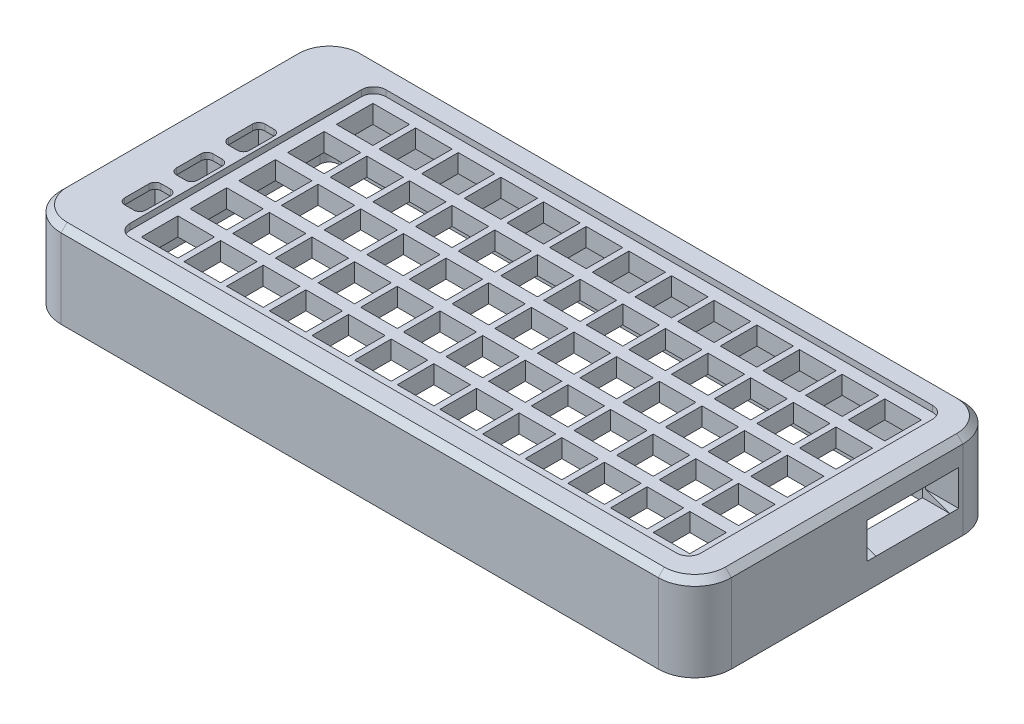
SolidWorks part; units mm, degrees
ref_plane "前视基准面" through (0, 0, 0) normal (0, 0, 1) x (1, 0, 0)
ref_plane "上视基准面" through (0, 0, 0) normal (0, 1, 0) x (1, 0, 0)
ref_plane "右视基准面" through (0, 0, 0) normal (1, 0, 0) x (0, 0, -1)
other "Configuration Table"
sketch "草图1" plane through (0, 0, 0) normal (0, 1, 0) x (1, 0, 0)
  line L1 (-55, -25) -> (55, -25)
  line L2 (-55, -25) -> (-55, 25)
  line L3 (-55, 25) -> (55, 25)
  line L4 (55, -25) -> (55, 25)
  line L5 (-55, -25) -> (55, 25) construction
  line L6 (-55, 25) -> (55, -25) construction
  point P0 (0, 0)
  dimension "D1" = 50
  dimension "D2" = 110
extrude "凸台-拉伸1" add sketch "草图1" along normal blind 3
sketch "草图2" plane through (0, 0, 0) normal (0, -1, 0) x (1, 0, 0)
  line L0 (46.3251, 14.2) -> (44.0251, 17.8) construction
  line L1 (48.1751, 11) -> (48.1751, 5)
  line L2 (48.1751, 19) -> (42.1751, 19)
  line L3 (48.1751, 19) -> (48.1751, 13)
  line L4 (48.1751, 13) -> (42.1751, 13)
  line L5 (42.1751, 19) -> (42.1751, 13)
  line L6 (48.1751, 19) -> (42.1751, 13) construction
  line L7 (48.1751, 13) -> (42.1751, 19) construction
  line L8 (48.1751, 5) -> (42.1751, 5)
  line L9 (42.1751, 11) -> (42.1751, 5)
  line L10 (48.1751, 11) -> (42.1751, 11)
  line L11 (48.1751, 3) -> (48.1751, -3)
  line L12 (48.1751, -3) -> (42.1751, -3)
  line L13 (42.1751, 3) -> (42.1751, -3)
  line L14 (48.1751, 3) -> (42.1751, 3)
  line L15 (48.1751, -5) -> (48.1751, -11)
  line L16 (48.1751, -11) -> (42.1751, -11)
  line L17 (42.1751, -5) -> (42.1751, -11)
  line L18 (48.1751, -5) -> (42.1751, -5)
  line L19 (48.1751, -13) -> (48.1751, -19)
  line L20 (48.1751, -19) -> (42.1751, -19)
  line L21 (42.1751, -13) -> (42.1751, -19)
  line L22 (48.1751, -13) -> (42.1751, -13)
  line L23 (41.1751, 11) -> (41.1751, 5)
  line L24 (41.1751, 5) -> (35.1751, 5)
  line L25 (35.1751, 11) -> (35.1751, 5)
  line L26 (41.1751, 11) -> (35.1751, 11)
  line L27 (41.1751, 3) -> (41.1751, -3)
  line L28 (41.1751, -3) -> (35.1751, -3)
  line L29 (35.1751, 3) -> (35.1751, -3)
  line L30 (41.1751, 3) -> (35.1751, 3)
  line L31 (41.1751, -5) -> (41.1751, -11)
  line L32 (41.1751, -11) -> (35.1751, -11)
  line L33 (35.1751, -5) -> (35.1751, -11)
  line L34 (41.1751, -5) -> (35.1751, -5)
  line L35 (41.1751, -13) -> (41.1751, -19)
  line L36 (41.1751, -19) -> (35.1751, -19)
  line L37 (35.1751, -13) -> (35.1751, -19)
  line L38 (41.1751, -13) -> (35.1751, -13)
  line L39 (34.1751, 11) -> (34.1751, 5)
  line L40 (34.1751, 5) -> (28.1751, 5)
  line L41 (28.1751, 11) -> (28.1751, 5)
  line L42 (34.1751, 11) -> (28.1751, 11)
  line L43 (34.1751, 3) -> (34.1751, -3)
  line L44 (34.1751, -3) -> (28.1751, -3)
  line L45 (28.1751, 3) -> (28.1751, -3)
  line L46 (34.1751, 3) -> (28.1751, 3)
  line L47 (34.1751, -5) -> (34.1751, -11)
  line L48 (34.1751, -11) -> (28.1751, -11)
  line L49 (28.1751, -5) -> (28.1751, -11)
  line L50 (34.1751, -5) -> (28.1751, -5)
  line L51 (34.1751, -13) -> (34.1751, -19)
  line L52 (34.1751, -19) -> (28.1751, -19)
  line L53 (28.1751, -13) -> (28.1751, -19)
  line L54 (34.1751, -13) -> (28.1751, -13)
  line L55 (27.1751, 11) -> (27.1751, 5)
  line L56 (27.1751, 5) -> (21.1751, 5)
  line L57 (21.1751, 11) -> (21.1751, 5)
  line L58 (27.1751, 11) -> (21.1751, 11)
  line L59 (27.1751, 3) -> (27.1751, -3)
  line L60 (27.1751, -3) -> (21.1751, -3)
  line L61 (21.1751, 3) -> (21.1751, -3)
  line L62 (27.1751, 3) -> (21.1751, 3)
  line L63 (27.1751, -5) -> (27.1751, -11)
  line L64 (27.1751, -11) -> (21.1751, -11)
  line L65 (21.1751, -5) -> (21.1751, -11)
  line L66 (27.1751, -5) -> (21.1751, -5)
  line L67 (27.1751, -13) -> (27.1751, -19)
  line L68 (27.1751, -19) -> (21.1751, -19)
  line L69 (21.1751, -13) -> (21.1751, -19)
  line L70 (27.1751, -13) -> (21.1751, -13)
  line L71 (20.1751, 11) -> (20.1751, 5)
  line L72 (20.1751, 5) -> (14.1751, 5)
  line L73 (14.1751, 11) -> (14.1751, 5)
  line L74 (20.1751, 11) -> (14.1751, 11)
  line L75 (20.1751, 3) -> (20.1751, -3)
  line L76 (20.1751, -3) -> (14.1751, -3)
  line L77 (14.1751, 3) -> (14.1751, -3)
  line L78 (20.1751, 3) -> (14.1751, 3)
  line L79 (20.1751, -5) -> (20.1751, -11)
  line L80 (20.1751, -11) -> (14.1751, -11)
  line L81 (14.1751, -5) -> (14.1751, -11)
  line L82 (20.1751, -5) -> (14.1751, -5)
  line L83 (20.1751, -13) -> (20.1751, -19)
  line L84 (20.1751, -19) -> (14.1751, -19)
  line L85 (14.1751, -13) -> (14.1751, -19)
  line L86 (20.1751, -13) -> (14.1751, -13)
  line L87 (13.1751, 11) -> (13.1751, 5)
  line L88 (13.1751, 5) -> (7.1751, 5)
  line L89 (7.1751, 11) -> (7.1751, 5)
  line L90 (13.1751, 11) -> (7.1751, 11)
  line L91 (13.1751, 3) -> (13.1751, -3)
  line L92 (13.1751, -3) -> (7.1751, -3)
  line L93 (7.1751, 3) -> (7.1751, -3)
  line L94 (13.1751, 3) -> (7.1751, 3)
  line L95 (13.1751, -5) -> (13.1751, -11)
  line L96 (13.1751, -11) -> (7.1751, -11)
  line L97 (7.1751, -5) -> (7.1751, -11)
  line L98 (13.1751, -5) -> (7.1751, -5)
  line L99 (13.1751, -13) -> (13.1751, -19)
  line L100 (13.1751, -19) -> (7.1751, -19)
  line L101 (7.1751, -13) -> (7.1751, -19)
  line L102 (13.1751, -13) -> (7.1751, -13)
  line L103 (6.1751, 11) -> (6.1751, 5)
  line L104 (6.1751, 5) -> (0.1751, 5)
  line L105 (0.1751, 11) -> (0.1751, 5)
  line L106 (6.1751, 11) -> (0.1751, 11)
  line L107 (6.1751, 3) -> (6.1751, -3)
  line L108 (6.1751, -3) -> (0.1751, -3)
  line L109 (0.1751, 3) -> (0.1751, -3)
  line L110 (6.1751, 3) -> (0.1751, 3)
  line L111 (6.1751, -5) -> (6.1751, -11)
  line L112 (6.1751, -11) -> (0.1751, -11)
  line L113 (0.1751, -5) -> (0.1751, -11)
  line L114 (6.1751, -5) -> (0.1751, -5)
  line L115 (6.1751, -13) -> (6.1751, -19)
  line L116 (6.1751, -19) -> (0.1751, -19)
  line L117 (0.1751, -13) -> (0.1751, -19)
  line L118 (6.1751, -13) -> (0.1751, -13)
  line L119 (-0.8249, 11) -> (-0.8249, 5)
  line L120 (-0.8249, 5) -> (-6.8249, 5)
  line L121 (-6.8249, 11) -> (-6.8249, 5)
  line L122 (-0.8249, 11) -> (-6.8249, 11)
  line L123 (-0.8249, 3) -> (-0.8249, -3)
  line L124 (-0.8249, -3) -> (-6.8249, -3)
  line L125 (-6.8249, 3) -> (-6.8249, -3)
  line L126 (-0.8249, 3) -> (-6.8249, 3)
  line L127 (-0.8249, -5) -> (-0.8249, -11)
  line L128 (-0.8249, -11) -> (-6.8249, -11)
  line L129 (-6.8249, -5) -> (-6.8249, -11)
  line L130 (-0.8249, -5) -> (-6.8249, -5)
  line L131 (-0.8249, -13) -> (-0.8249, -19)
  line L132 (-0.8249, -19) -> (-6.8249, -19)
  line L133 (-6.8249, -13) -> (-6.8249, -19)
  line L134 (-0.8249, -13) -> (-6.8249, -13)
  line L135 (-7.8249, 11) -> (-7.8249, 5)
  line L136 (-7.8249, 5) -> (-13.8249, 5)
  line L137 (-13.8249, 11) -> (-13.8249, 5)
  line L138 (-7.8249, 11) -> (-13.8249, 11)
  line L139 (-7.8249, 3) -> (-7.8249, -3)
  line L140 (-7.8249, -3) -> (-13.8249, -3)
  line L141 (-13.8249, 3) -> (-13.8249, -3)
  line L142 (-7.8249, 3) -> (-13.8249, 3)
  line L143 (-7.8249, -5) -> (-7.8249, -11)
  line L144 (-7.8249, -11) -> (-13.8249, -11)
  line L145 (-13.8249, -5) -> (-13.8249, -11)
  line L146 (-7.8249, -5) -> (-13.8249, -5)
  line L147 (-7.8249, -13) -> (-7.8249, -19)
  line L148 (-7.8249, -19) -> (-13.8249, -19)
  line L149 (-13.8249, -13) -> (-13.8249, -19)
  line L150 (-7.8249, -13) -> (-13.8249, -13)
  line L151 (-14.8249, 11) -> (-14.8249, 5)
  line L152 (-14.8249, 5) -> (-20.8249, 5)
  line L153 (-20.8249, 11) -> (-20.8249, 5)
  line L154 (-14.8249, 11) -> (-20.8249, 11)
  line L155 (-14.8249, 3) -> (-14.8249, -3)
  line L156 (-14.8249, -3) -> (-20.8249, -3)
  line L157 (-20.8249, 3) -> (-20.8249, -3)
  line L158 (-14.8249, 3) -> (-20.8249, 3)
  line L159 (-14.8249, -5) -> (-14.8249, -11)
  line L160 (-14.8249, -11) -> (-20.8249, -11)
  line L161 (-20.8249, -5) -> (-20.8249, -11)
  line L162 (-14.8249, -5) -> (-20.8249, -5)
  line L163 (-14.8249, -13) -> (-14.8249, -19)
  line L164 (-14.8249, -19) -> (-20.8249, -19)
  line L165 (-20.8249, -13) -> (-20.8249, -19)
  line L166 (-14.8249, -13) -> (-20.8249, -13)
  line L167 (-21.8249, 11) -> (-21.8249, 5)
  line L168 (-21.8249, 5) -> (-27.8249, 5)
  line L169 (-27.8249, 11) -> (-27.8249, 5)
  line L170 (-21.8249, 11) -> (-27.8249, 11)
  line L171 (-21.8249, 3) -> (-21.8249, -3)
  line L172 (-21.8249, -3) -> (-27.8249, -3)
  line L173 (-27.8249, 3) -> (-27.8249, -3)
  line L174 (-21.8249, 3) -> (-27.8249, 3)
  line L175 (-21.8249, -5) -> (-21.8249, -11)
  line L176 (-21.8249, -11) -> (-27.8249, -11)
  line L177 (-27.8249, -5) -> (-27.8249, -11)
  line L178 (-21.8249, -5) -> (-27.8249, -5)
  line L179 (-21.8249, -13) -> (-21.8249, -19)
  line L180 (-21.8249, -19) -> (-27.8249, -19)
  line L181 (-27.8249, -13) -> (-27.8249, -19)
  line L182 (-21.8249, -13) -> (-27.8249, -13)
  line L183 (-28.8249, 11) -> (-28.8249, 5)
  line L184 (-28.8249, 5) -> (-34.8249, 5)
  line L185 (-34.8249, 11) -> (-34.8249, 5)
  line L186 (-28.8249, 11) -> (-34.8249, 11)
  line L187 (-28.8249, 3) -> (-28.8249, -3)
  line L188 (-28.8249, -3) -> (-34.8249, -3)
  line L189 (-34.8249, 3) -> (-34.8249, -3)
  line L190 (-28.8249, 3) -> (-34.8249, 3)
  line L191 (-28.8249, -5) -> (-28.8249, -11)
  line L192 (-28.8249, -11) -> (-34.8249, -11)
  line L193 (-34.8249, -5) -> (-34.8249, -11)
  line L194 (-28.8249, -5) -> (-34.8249, -5)
  line L195 (-28.8249, -13) -> (-28.8249, -19)
  line L196 (-28.8249, -19) -> (-34.8249, -19)
  line L197 (-34.8249, -13) -> (-34.8249, -19)
  line L198 (-28.8249, -13) -> (-34.8249, -13)
  line L199 (-35.8249, 11) -> (-35.8249, 5)
  line L200 (-35.8249, 5) -> (-41.8249, 5)
  line L201 (-41.8249, 11) -> (-41.8249, 5)
  line L202 (-35.8249, 11) -> (-41.8249, 11)
  line L203 (-35.8249, 3) -> (-35.8249, -3)
  line L204 (-35.8249, -3) -> (-41.8249, -3)
  line L205 (-41.8249, 3) -> (-41.8249, -3)
  line L206 (-35.8249, 3) -> (-41.8249, 3)
  line L207 (-35.8249, -5) -> (-35.8249, -11)
  line L208 (-35.8249, -11) -> (-41.8249, -11)
  line L209 (-41.8249, -5) -> (-41.8249, -11)
  line L210 (-35.8249, -5) -> (-41.8249, -5)
  line L211 (-35.8249, -13) -> (-35.8249, -19)
  line L212 (-35.8249, -19) -> (-41.8249, -19)
  line L213 (-41.8249, -13) -> (-41.8249, -19)
  line L214 (-35.8249, -13) -> (-41.8249, -13)
  line L215 (41.1751, 19) -> (41.1751, 13)
  line L216 (41.1751, 13) -> (35.1751, 13)
  line L217 (35.1751, 19) -> (35.1751, 13)
  line L218 (41.1751, 19) -> (35.1751, 19)
  line L219 (34.1751, 19) -> (34.1751, 13)
  line L220 (34.1751, 13) -> (28.1751, 13)
  line L221 (28.1751, 19) -> (28.1751, 13)
  line L222 (34.1751, 19) -> (28.1751, 19)
  line L223 (27.1751, 19) -> (27.1751, 13)
  line L224 (27.1751, 13) -> (21.1751, 13)
  line L225 (21.1751, 19) -> (21.1751, 13)
  line L226 (27.1751, 19) -> (21.1751, 19)
  line L227 (20.1751, 19) -> (20.1751, 13)
  line L228 (20.1751, 13) -> (14.1751, 13)
  line L229 (14.1751, 19) -> (14.1751, 13)
  line L230 (20.1751, 19) -> (14.1751, 19)
  line L231 (13.1751, 19) -> (13.1751, 13)
  line L232 (13.1751, 13) -> (7.1751, 13)
  line L233 (7.1751, 19) -> (7.1751, 13)
  line L234 (13.1751, 19) -> (7.1751, 19)
  line L235 (6.1751, 19) -> (6.1751, 13)
  line L236 (6.1751, 13) -> (0.1751, 13)
  line L237 (0.1751, 19) -> (0.1751, 13)
  line L238 (6.1751, 19) -> (0.1751, 19)
  line L239 (-0.8249, 19) -> (-0.8249, 13)
  line L240 (-0.8249, 13) -> (-6.8249, 13)
  line L241 (-6.8249, 19) -> (-6.8249, 13)
  line L242 (-0.8249, 19) -> (-6.8249, 19)
  line L243 (-7.8249, 19) -> (-7.8249, 13)
  line L244 (-7.8249, 13) -> (-13.8249, 13)
  line L245 (-13.8249, 19) -> (-13.8249, 13)
  line L246 (-7.8249, 19) -> (-13.8249, 19)
  line L247 (-14.8249, 19) -> (-14.8249, 13)
  line L248 (-14.8249, 13) -> (-20.8249, 13)
  line L249 (-20.8249, 19) -> (-20.8249, 13)
  line L250 (-14.8249, 19) -> (-20.8249, 19)
  line L251 (-21.8249, 19) -> (-21.8249, 13)
  line L252 (-21.8249, 13) -> (-27.8249, 13)
  line L253 (-27.8249, 19) -> (-27.8249, 13)
  line L254 (-21.8249, 19) -> (-27.8249, 19)
  line L255 (-28.8249, 19) -> (-28.8249, 13)
  line L256 (-28.8249, 13) -> (-34.8249, 13)
  line L257 (-34.8249, 19) -> (-34.8249, 13)
  line L258 (-28.8249, 19) -> (-34.8249, 19)
  line L259 (-35.8249, 19) -> (-35.8249, 13)
  line L260 (-35.8249, 13) -> (-41.8249, 13)
  line L261 (-41.8249, 19) -> (-41.8249, 13)
  line L262 (-35.8249, 19) -> (-41.8249, 19)
  point P2 (45.1751, 16)
  dimension "D1" = 6
  dimension "D2" = 6
  dimension "D3" = 5
  dimension "D4" = 13
extrude "切除-拉伸1" cut sketch "草图2" against normal blind 10
sketch "草图3" plane through (0, 3, 0) normal (0, 1, 0) x (1, 0, 0)
  line L0 (-55, 25) -> (-55, -25) construction
  line L1 (-55, 25) -> (55, 25)
  line L2 (-55, 25) -> (-55, -25)
  line L3 (-55, -25) -> (55, -25)
  line L4 (55, 25) -> (55, -25)
  line L5 (55, 25) -> (-55, 25) construction
  line L6 (55, -25) -> (55, 25) construction
  line L7 (-55, -25) -> (55, -25) construction
  line L9 (-43.7, 21) -> (50, 21)
  line L10 (-43.7, 21) -> (-43.7, -21)
  line L11 (-43.7, -21) -> (50, -21)
  line L12 (50, 21) -> (50, -21)
  dimension "D1" = 4
  dimension "D2" = 4
  dimension "D3" = 5
  dimension "D4" = 42
  dimension "D5" = 11.3
extrude "凸台-拉伸2" add sketch "草图3" along normal blind 1
fillet "圆角1" radius 6 4 edges at (-55, 2, -25) (-55, 2, 25) (55, 2, 25) (55, 2, -25)
sketch "草图4" plane through (0, 0, 0) normal (0, -1, 0) x (1, 0, 0)
  line L0 (-45.3973, -4.764) -> (-46.6251, -1.636) construction
  line L1 (-45.3973, 3.736) -> (-46.6251, 6.864) construction
  line L2 (-45.2612, -0.2) -> (-46.7612, -0.2)
  line L3 (-44.2612, -1.2) -> (-44.2612, -5.2)
  line L4 (-45.2612, -6.2) -> (-46.7612, -6.2)
  line L5 (-47.7612, -1.2) -> (-47.7612, -5.2)
  line L6 (-44.2612, -0.2) -> (-47.7612, -6.2) construction
  line L7 (-44.2612, -6.2) -> (-47.7612, -0.2) construction
  line L8 (-44.2612, 7.3) -> (-44.2612, 3.3)
  line L9 (-45.2612, 8.3) -> (-46.7612, 8.3)
  line L10 (-47.7612, 7.3) -> (-47.7612, 3.3)
  line L11 (-45.2612, 2.3) -> (-46.7612, 2.3)
  line L12 (-45.3973, 12.236) -> (-46.6251, 15.364) construction
  line L13 (-44.2612, 15.8) -> (-44.2612, 11.8)
  line L14 (-45.2612, 16.8) -> (-46.7612, 16.8)
  line L15 (-47.7612, 15.8) -> (-47.7612, 11.8)
  line L16 (-45.2612, 10.8) -> (-46.7612, 10.8)
  arc A0 (-46.7612, 16.8) -> (-47.7612, 15.8) centre (-46.7612, 15.8) ccw
  arc A1 (-44.2612, 11.8) -> (-45.2612, 10.8) centre (-45.2612, 11.8) cw
  arc A2 (-44.2612, 15.8) -> (-45.2612, 16.8) centre (-45.2612, 15.8) ccw
  arc A3 (-47.7612, 11.8) -> (-46.7612, 10.8) centre (-46.7612, 11.8) ccw
  arc A4 (-46.7612, 8.3) -> (-47.7612, 7.3) centre (-46.7612, 7.3) ccw
  arc A5 (-44.2612, 3.3) -> (-45.2612, 2.3) centre (-45.2612, 3.3) cw
  arc A6 (-44.2612, 7.3) -> (-45.2612, 8.3) centre (-45.2612, 7.3) ccw
  arc A7 (-47.7612, 3.3) -> (-46.7612, 2.3) centre (-46.7612, 3.3) ccw
  arc A8 (-46.7612, -0.2) -> (-47.7612, -1.2) centre (-46.7612, -1.2) ccw
  arc A9 (-44.2612, -5.2) -> (-45.2612, -6.2) centre (-45.2612, -5.2) cw
  arc A10 (-45.2612, -0.2) -> (-44.2612, -1.2) centre (-45.2612, -1.2) cw
  arc A11 (-46.7612, -6.2) -> (-47.7612, -5.2) centre (-46.7612, -5.2) cw
  point P2 (-46.0112, -3.2)
  dimension "D4" = 1
  dimension "D1" = 3.5
  dimension "D2" = 6
  dimension "D3" = 3
extrude "切除-拉伸2" cut sketch "草图4" against normal blind 6
sketch "草图5" plane through (0, 0, 0) normal (0, -1, 0) x (1, 0, 0)
  line L0 (-46.0112, -6.2) -> (-46.0112, -0.2) construction
  line L1 (-46.7612, -6.2) -> (-45.2612, -6.2) construction
  line L2 (-45.2612, -0.2) -> (-46.7612, -0.2) construction
  line L3 (-43.7612, 8.8) -> (-43.7612, 1.8)
  line L4 (-43.7612, 0.3) -> (-48.2612, 0.3)
  line L5 (-43.7612, 0.3) -> (-43.7612, -6.7)
  line L6 (-43.7612, -6.7) -> (-48.2612, -6.7)
  line L7 (-48.2612, 0.3) -> (-48.2612, -6.7)
  line L8 (-43.7612, 0.3) -> (-48.2612, -6.7) construction
  line L9 (-43.7612, -6.7) -> (-48.2612, 0.3) construction
  line L10 (-43.7612, 8.8) -> (-48.2612, 8.8)
  line L11 (-48.2612, 8.8) -> (-48.2612, 1.8)
  line L12 (-43.7612, 1.8) -> (-48.2612, 1.8)
  line L13 (-43.7612, 17.3) -> (-43.7612, 10.3)
  line L14 (-43.7612, 17.3) -> (-48.2612, 17.3)
  line L15 (-48.2612, 17.3) -> (-48.2612, 10.3)
  line L16 (-43.7612, 10.3) -> (-48.2612, 10.3)
  point P6 (-46.0112, -3.2)
  dimension "D1" = 7
  dimension "D2" = 4.5
  dimension "D3" = 3
extrude "切除-拉伸3" cut sketch "草图5" against normal blind 3
fillet "圆角2" radius 2 4 edges at (50, 3.5, 21) (50, 3.5, -21) (-43.7, 3.5, -21) (-43.7, 3.5, 21)
chamfer "倒角1" distance 1 angle 45 8 edges at (53.2426, 4, -23.2426) (0, 4, -25) (55, 4, 0) (-53.2426, 4, -23.2426) (53.2426, 4, 23.2426) (-55, 4, 0) (0, 4, 25) (-53.2426, 4, 23.2426)
sketch "草图6" plane through (0, 0, 0) normal (0, -1, 0) x (1, 0, 0)
  line L6 (-55, 19) -> (-55, -19)
  line L7 (-49, -25) -> (49, -25)
  line L8 (-55, 19) -> (-55, -19)
  line L9 (-49, -25) -> (49, -25)
  line L10 (55, 19) -> (55, -19)
  line L11 (55, 19) -> (55, -19)
  line L13 (50.5, 19) -> (50.5, -19)
  line L14 (49, 25) -> (-49, 25)
  line L15 (49, 25) -> (-49, 25)
  line L16 (49, 20.5) -> (-49, 20.5)
  line L17 (-50.5, 19) -> (-50.5, -19)
  line L18 (-49, -20.5) -> (49, -20.5)
  arc A8 (-55, -19) -> (-49, -25) centre (-49, -19) ccw
  arc A9 (49, -25) -> (55, -19) centre (49, -19) ccw
  arc A10 (-55, -19) -> (-49, -25) centre (-49, -19) ccw
  arc A11 (49, -25) -> (55, -19) centre (49, -19) ccw
  arc A14 (49, -20.5) -> (50.5, -19) centre (49, -19) ccw
  arc A15 (50.5, 19) -> (49, 20.5) centre (49, 19) ccw
  arc A16 (-49, 25) -> (-55, 19) centre (-49, 19) ccw
  arc A17 (55, 19) -> (49, 25) centre (49, 19) ccw
  arc A18 (-49, 25) -> (-55, 19) centre (-49, 19) ccw
  arc A19 (55, 19) -> (49, 25) centre (49, 19) ccw
  arc A20 (-49, 20.5) -> (-50.5, 19) centre (-49, 19) ccw
  arc A21 (-50.5, -19) -> (-49, -20.5) centre (-49, -19) ccw
  dimension "D1" = 0
  dimension "D2" = 0
  dimension "D3" = 0
  dimension "D4" = 4.5
extrude "凸台-拉伸3" add sketch "草图6" along normal blind 10
sketch "草图8" plane through (-50.5, 0, 0) normal (1, 0, 0) x (0, 0, -1)
  line L0 (15.184, -3.2801) -> (8.184, -3.2801) construction
  line L1 (14.6841, -3.2801) -> (8.6839, -3.2801) construction
  line L2 (14.6841, -5.0285) -> (8.6839, -5.0285)
  line L3 (14.6841, -1.5316) -> (8.6839, -1.5316)
  arc A0 (14.6841, -5.0285) -> (14.6841, -1.5316) centre (14.6841, -3.2801) ccw
  arc A1 (8.6839, -1.5316) -> (8.6839, -5.0285) centre (8.6839, -3.2801) ccw
  point P4 (11.684, -3.2801)
extrude "切除-拉伸4" cut sketch "草图8" against normal blind 7
sketch "草图9" plane through (-55, 0, 0) normal (-1, 0, 0) x (0, 0, 1)
  line L0 (-15.0883, -3.2801) -> (-8.2797, -3.2801) construction
  line L1 (-15.0883, -0.0301) -> (-8.2797, -0.0301)
  line L4 (-15.0883, -6.5301) -> (-8.2797, -6.5301)
  line L5 (-14.6841, -1.5316) -> (-8.6839, -1.5316) construction
  arc A6 (-15.0883, -0.0301) -> (-15.0883, -6.5301) centre (-15.0883, -3.2801) ccw
  arc A7 (-8.2797, -6.5301) -> (-8.2797, -0.0301) centre (-8.2797, -3.2801) ccw
  point P2 (-11.684, -3.2801)
  point P8 (-11.684, -3.2801)
  dimension "D3" = 3.25
  dimension "D1" = 6.5
  dimension "D2" = 1.5015
extrude "切除-拉伸5" cut sketch "草图9" against normal blind 3.5
sketch "草图10" plane through (50.5, 0, 0) normal (-1, 0, 0) x (0, 0, 1)
  line L1 (-4.7442, -1.4441) -> (-16.8485, -1.4441)
  line L2 (-4.7442, -1.4441) -> (-4.7442, -4.3565)
  line L3 (-4.7442, -4.3565) -> (-16.8485, -4.3565)
  line L4 (-16.8485, -1.4441) -> (-16.8485, -4.3565)
extrude "切除-拉伸6" cut sketch "草图10" against normal blind 6.5
chamfer "倒角2" distance 4 angle 20 1 edges at (55, -1.4441, -10.7963) first distance on face at (52.75, -1.4441, -10.7963)
chamfer "倒角3" distance 4 angle 20 1 edges at (55, -4.3565, -10.7963) first distance on face at (52.75, -4.3565, -10.7963)
chamfer "倒角4" distance 4 angle 20 1 edges at (55, -2.9003, -4.7442) first distance on face at (52.1667, -2.9003, -4.7442)
chamfer "倒角5" distance 4 angle 20 1 edges at (55, -2.9003, -16.8485) first distance on face at (52.1667, -2.9003, -16.8485)
sketch "草图11" plane through (0, -10, 0) normal (0, -1, 0) x (1, 0, 0)
  line L0 (-49, -25) -> (49, -25) construction
  line L2 (0, 0) -> (50000, 0) construction
  circle A0 centre (0, -22.7) radius 1.55
  circle A1 centre (20, -22.7) radius 1.55
  circle A2 centre (40, -22.7) radius 1.55
  circle A3 centre (-20, -22.7) radius 1.55
  circle A4 centre (-40, -22.7) radius 1.55
  circle A5 centre (-40, 22.7) radius 1.55
  circle A6 centre (-20, 22.7) radius 1.55
  circle A7 centre (40, 22.7) radius 1.55
  circle A8 centre (20, 22.7) radius 1.55
  circle A9 centre (0, 22.7) radius 1.55
  dimension "D1" = 3.1
  dimension "D3" = 3
  dimension "D2" = 2.3
  dimension "D4" = 3
extrude "切除-拉伸7" cut sketch "草图11" against normal blind 2
sketch "草图12" plane through (0, 0, -4.7442) normal (0, 0, -1) x (-1, 0, 0)
  line L1 (-50.5, -4.3565) -> (-55, -4.3565)
  line L2 (-50.5, -4.3565) -> (-50.5, -5.8123)
  line L3 (-50.5, -5.8123) -> (-55, -5.8123)
  line L4 (-55, -4.3565) -> (-55, -5.8123)
extrude "切除-拉伸9" cut sketch "草图12" along normal up to surface (12.1043 mm away) up to face at (50.75, -2.9003, -16.8485)
